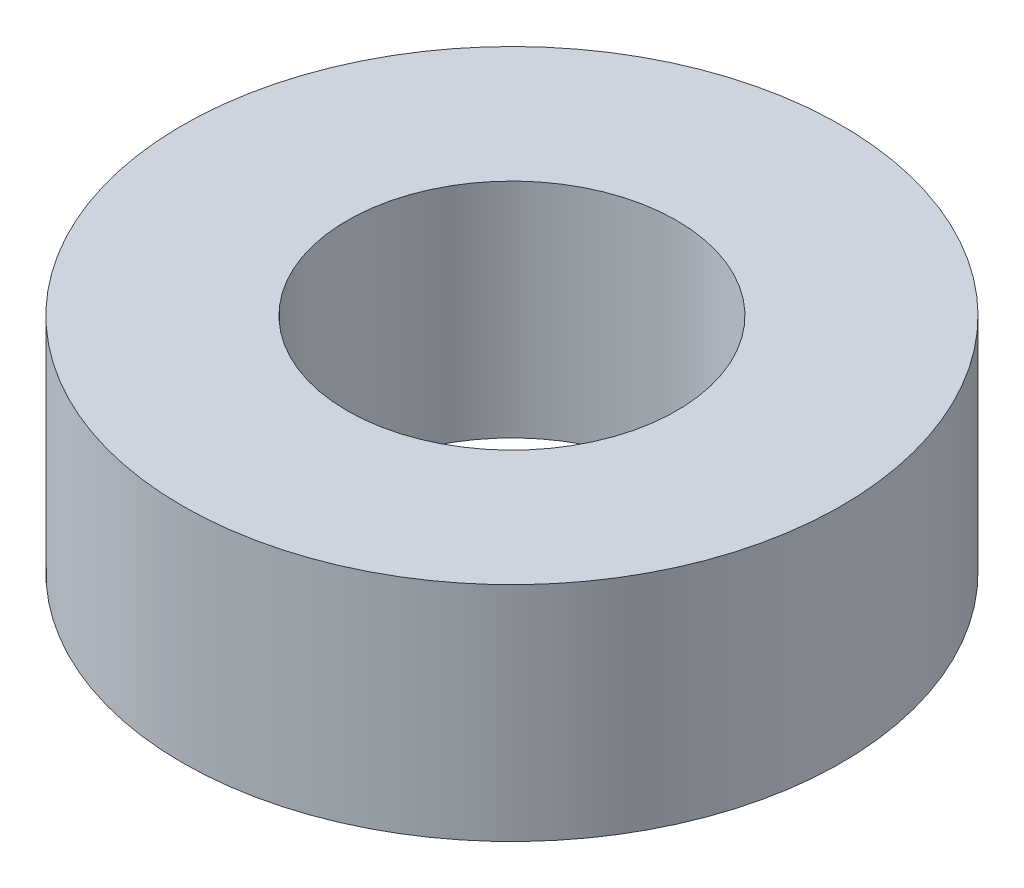
SolidWorks part; units mm, degrees
ref_plane "Front Plane" through (0, 0, 0) normal (0, 0, 1) x (1, 0, 0)
ref_plane "Top Plane" through (0, 0, 0) normal (0, 1, 0) x (1, 0, 0)
ref_plane "Right Plane" through (0, 0, 0) normal (1, 0, 0) x (0, 0, -1)
sketch "Sketch1" plane through (0, 0, 0) normal (0, 1, 0) x (1, 0, 0)
  circle A0 centre (0, 0) radius 40
  dimension "FLANGE_OD" = 80
extrude "Boss-Extrude1" add sketch "Sketch1" along normal blind 27
sketch "Sketch2" plane through (0, 0, 0) normal (0, 1, 0) x (1, 0, 0)
  circle A0 centre (0, 0) radius 20
  dimension "BORE_D" = 40
extrude "Cut-Extrude1" cut sketch "Sketch2" along normal through all
sketch "Sketch3" plane through (0, 27, 0) normal (0, 1, 0) x (1, 0, 0)
  circle A0 centre (0, 0) radius 14.2249 construction
  circle A1 centre (-14.2249, 0) radius 1.7538
  dimension "BOLT_D" = 3.5076
  dimension "BOLT_PCD" = 28.4499
extrude "Cut-Extrude2" cut sketch "Sketch3" against normal blind 20.3016 rebuild error yes
pattern_circular "CirPattern1" count 8 over 360 rebuild error yes
